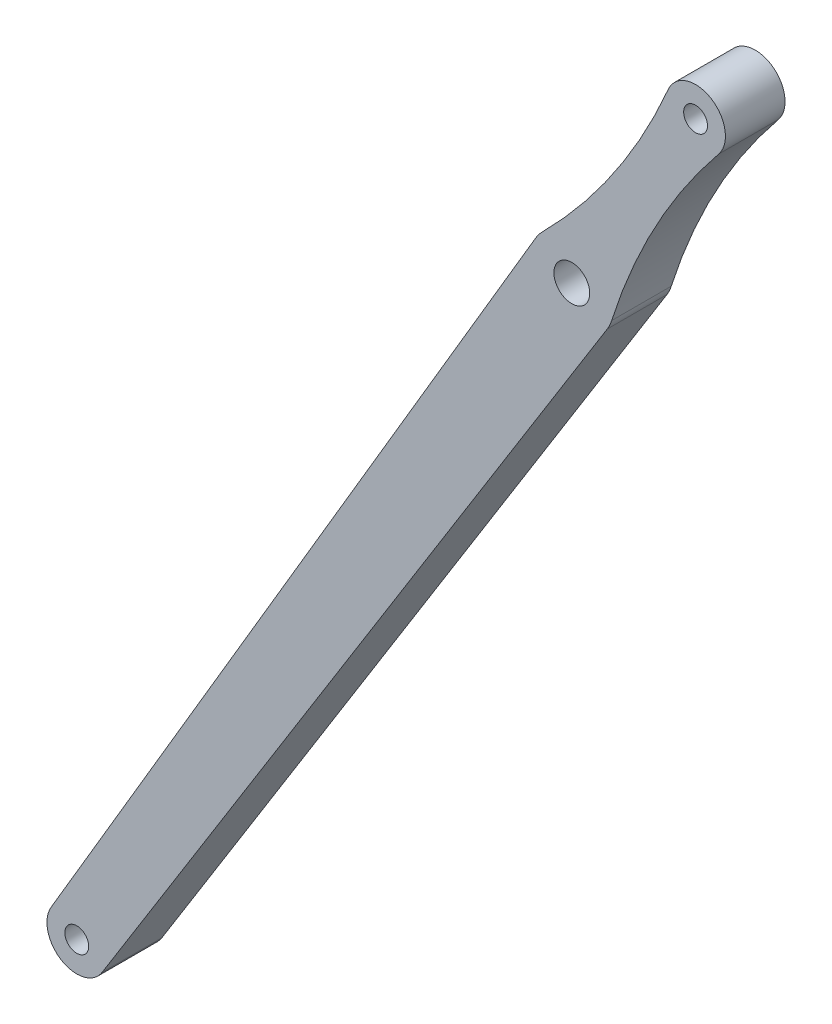
SolidWorks part; units mm, degrees
ref_plane "Front Plane" through (0, 0, 0) normal (0, 0, 1) x (1, 0, 0)
ref_plane "Top Plane" through (0, 0, 0) normal (0, 1, 0) x (1, 0, 0)
ref_plane "Right Plane" through (0, 0, 0) normal (1, 0, 0) x (0, 0, -1)
sketch "Sketch1" plane through (0, 0, 0) normal (0, 0, 1) x (1, 0, 0)
  line L0 (-157.8699, 102.3552) -> (-239.1321, -35.4579)
  line L3 (-145.901, 95.0946) -> (-230.5829, -40.644)
  circle A2 centre (-151.8401, 98.7997) radius 7
  circle A3 centre (-234.8251, -37.9975) radius 5
  circle A4 centre (-131.0938, 132.9991) radius 5
  arc A5 (-156.7968, 103.7425) -> (-135.6897, 134.9683) centre (-227.6072, 174.3534) ccw
  arc A6 (-127.2241, 129.8328) -> (-145.1665, 96.6872) centre (-49.829, 66.5083) ccw
  circle A7 centre (-234.8251, -37.9975) radius 2 construction
  circle A8 centre (-234.8251, -37.9975) radius 2
  circle A9 centre (-151.8401, 98.7997) radius 3 construction
  circle A10 centre (-151.8401, 98.7997) radius 3
  circle A11 centre (-131.0938, 132.9991) radius 2 construction
  circle A12 centre (-131.0938, 132.9991) radius 2
  dimension "D1" = 14
  dimension "D2" = 10
  dimension "D3" = 10
  dimension "D4" = 100
  dimension "D5" = 100
extrude "Boss-Extrude1" add sketch "Sketch1" along normal blind 5 and the other way blind 5 contours A3 L3 A2 L0 | A3 | A2 | A6 A4 A5 A2 | A4 region at (-191.7042, 33.0853, 0) region at (-157.2204, 102.9615, 0) region at (-233.546, -33.3103, 0) region at (-141.3893, 116.0275, 0) region at (-130.1171, 137.7585, 0)
